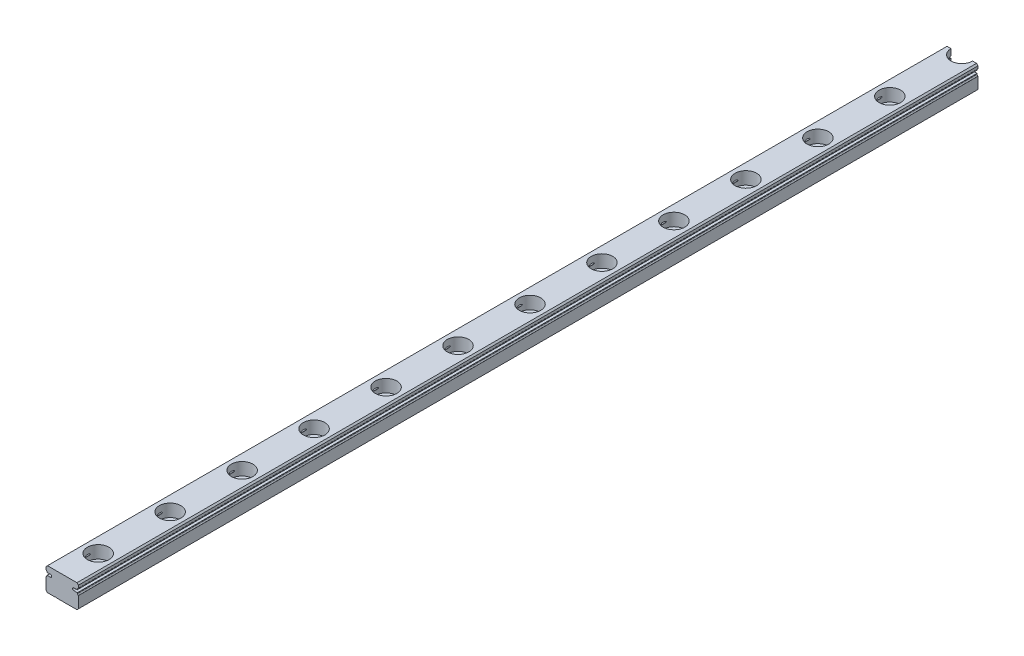
SolidWorks part; units mm, degrees
ref_plane "Alzado" through (0, 0, 0) normal (0, 0, 1) x (1, 0, 0)
ref_plane "Planta" through (0, 0, 0) normal (0, 1, 0) x (1, 0, 0)
ref_plane "Vista lateral" through (0, 0, 0) normal (1, 0, 0) x (0, 0, -1)
ref_plane "Plano1" through (0, 3.3057, 0) normal (0, 1, 0) x (1, 0, 0)
sketch "Croquis1" plane through (0, 3.3057, 0) normal (0, 1, 0) x (1, 0, 0)
  line L0 (4.5, 0) -> (-4.5, 0)
  line L1 (-4.5, 0) -> (-4.5, -250)
  line L2 (-4.5, -250) -> (4.5, -250)
  line L3 (4.5, -250) -> (4.5, 0)
  dimension "D1" = 9
  dimension "D2" = 250
extrude "Saliente-Extruir1" add sketch "Croquis1" against normal blind 6.5
sketch "Croquis2" plane through (0, 0, 0) normal (0, 0, -1) x (-1, 0, 0)
  line L0 (1.6, -3.1943) -> (2.1, -3.1943)
  arc A0 (2.1, -3.1943) -> (1.6, -3.1943) centre (1.85, -3.4568) ccw
extrude "Cortar-Extruir1" cut sketch "Croquis2" against normal through all
sketch "Croquis3" plane through (0, 0, 0) normal (0, 0, -1) x (-1, 0, 0)
  line L0 (-4.5, 1.6457) -> (-4.5, 0.9457)
  line L1 (-4.5, 0.9457) -> (-3.25, 0.9457)
  line L2 (-3.25, 1.6457) -> (-4.5, 1.6457)
  arc A0 (-3.25, 0.9457) -> (-3.25, 1.6457) centre (-3.25, 1.2957) ccw
extrude "Cortar-Extruir2" cut sketch "Croquis3" against normal through all
sketch "Croquis4" plane through (0, 0, 0) normal (0, 0, -1) x (-1, 0, 0)
  line L0 (-4.3353, 0.9457) -> (-4.5, 0.9457)
  line L1 (-4.5, 0.9457) -> (-4.5, 0.4169)
  arc A0 (-4.5, 0.4169) -> (-4.3353, 0.9457) centre (-4.622, 0.745) ccw
extrude "Cortar-Extruir3" cut sketch "Croquis4" against normal through all
sketch "Croquis5" plane through (0, 0, 0) normal (0, 0, -1) x (-1, 0, 0)
  line L0 (-4.5, 2.1744) -> (-4.5, 1.6457)
  line L1 (-4.5, 1.6457) -> (-4.3353, 1.6457)
  arc A0 (-4.3353, 1.6457) -> (-4.5, 2.1744) centre (-4.622, 1.8464) ccw
extrude "Cortar-Extruir4" cut sketch "Croquis5" against normal through all
sketch "Croquis6" plane through (0, 0, 0) normal (0, 0, -1) x (-1, 0, 0)
  line L0 (4.5, 0.9457) -> (4.5, 1.6457)
  line L1 (4.5, 1.6457) -> (3.25, 1.6457)
  line L2 (3.25, 0.9457) -> (4.5, 0.9457)
  arc A0 (3.25, 1.6457) -> (3.25, 0.9457) centre (3.25, 1.2957) ccw
extrude "Cortar-Extruir5" cut sketch "Croquis6" against normal through all
sketch "Croquis7" plane through (0, 0, 0) normal (0, 0, -1) x (-1, 0, 0)
  line L0 (4.3353, 1.6457) -> (4.5, 1.6457)
  line L1 (4.5, 1.6457) -> (4.5, 2.1744)
  arc A0 (4.5, 2.1744) -> (4.3353, 1.6457) centre (4.622, 1.8464) ccw
extrude "Cortar-Extruir6" cut sketch "Croquis7" against normal through all
sketch "Croquis8" plane through (0, 0, 0) normal (0, 0, -1) x (-1, 0, 0)
  line L0 (4.5, 0.4169) -> (4.5, 0.9457)
  line L1 (4.5, 0.9457) -> (4.3353, 0.9457)
  arc A0 (4.3353, 0.9457) -> (4.5, 0.4169) centre (4.622, 0.745) ccw
extrude "Cortar-Extruir7" cut sketch "Croquis8" against normal through all
hole_wizard "Refrentado para tornillo con cabeza hexagonal de M31" positions "Croquis10" profile "Croquis9" counterbore size "M3" standard "Ansi Metric"
sketch "Croquis10" plane through (0, 3.3057, 0) normal (0, 1, 0) x (1, 0, 0)
  point P0 (0, -240)
  point P1 (0, -220)
  point P2 (0, -200)
  point P3 (0, -180)
  point P4 (0, -160)
  point P5 (0, -140)
  point P6 (0, -120)
  point P7 (0, -100)
  point P8 (0, -80)
  point P9 (0, -60)
  point P10 (0, -40)
  point P11 (0, -20)
  point P12 (0, 0)
  point P13 (0, 20)
  point P14 (0, 40)
  point P15 (0, 60)
  point P16 (0, 80)
  point P17 (0, 100)
  point P18 (0, 120)
  point P19 (0, 140)
  point P20 (0, 160)
  point P21 (0, 180)
  point P22 (0, 200)
  point P23 (0, 220)
  point P24 (0, 240)
sketch "Croquis9" plane through (0, 3.3057, 240) normal (1, 0, 0) x (0, 0, 1)
  line L0 (0, 0) -> (0, 6.5)
  line L1 (0, 6.5) -> (1.75, 6.5)
  line L3 (1.75, 6.5) -> (1.75, 3.5)
  line L4 (1.75, 3.5) -> (3, 3.5)
  line L5 (3, 3.5) -> (3, 0)
  line L7 (3, 0) -> (0, 0)
  line L11 (0, -6.35) -> (0, 107.95) construction
  dimension "Diámetro de taladro hasta el siguiente" = 3.5
  dimension "Profundidad de taladro hasta el siguiente" = 6.5
  dimension "Diámetro de refrentado" = 6
  dimension "Profundidad de refrentado" = 3.5
chamfer "Chaflán1" distance 0.4 angle 45 4 edges at (-4.5, -3.1943, 125) (-4.5, 3.3057, 125) (4.5, -3.1943, 125) (4.5, 3.3057, 125)
chamfer "Chaflán2" distance 0.011 angle 36.529 4 edges at (-4.5, 2.1744, 125) (4.5, 0.4169, 125) (-4.5, 0.4169, 125) (4.5, 2.1744, 125) first distance on face at (-4.3528, 1.9303, 125) first distance on face at (4.3528, 0.6611, 125) first distance on face at (-4.5, -1.1887, 125) first distance on face at (4.5, 2.5401, 125)
chamfer "Chaflán3" distance 0.151 angle 53.471 4 edges at (-4.3353, 0.9457, 125) (4.3353, 0.9457, 125) (-4.3353, 1.6457, 125) (4.3353, 1.6457, 125) first distance on face at (-3.7926, 0.9457, 125) first distance on face at (4.3493, 0.6648, 125) first distance on face at (-4.3493, 1.9266, 125) first distance on face at (3.7926, 1.6457, 125)
